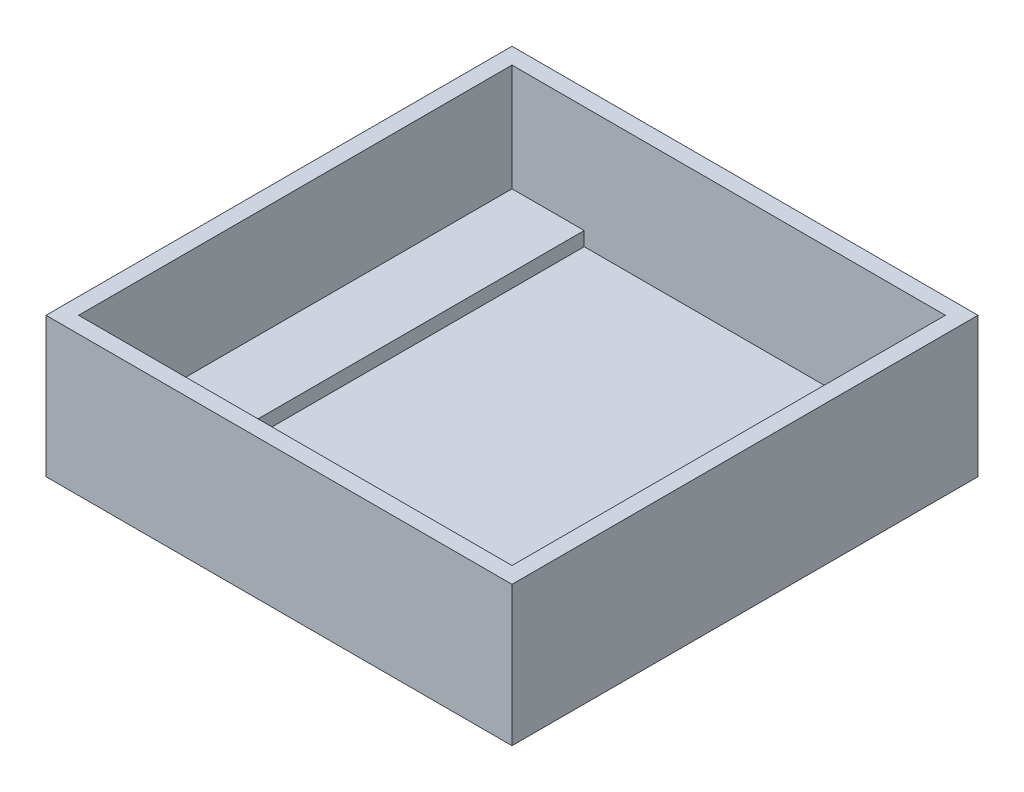
SolidWorks part; units mm, degrees
ref_plane "Front Plane" through (0, 0, 0) normal (0, 0, 1) x (1, 0, 0)
ref_plane "Top Plane" through (0, 0, 0) normal (0, 1, 0) x (1, 0, 0)
ref_plane "Right Plane" through (0, 0, 0) normal (1, 0, 0) x (0, 0, -1)
sketch "Sketch1" plane through (0, 0, 0) normal (0, 1, 0) x (1, 0, 0)
  line L0 (-310, 465) -> (-465, 465)
  line L1 (-500, -500) -> (500, -500)
  line L2 (-500, -500) -> (-500, 500)
  line L3 (-500, 500) -> (500, 500)
  line L4 (500, -500) -> (500, 500)
  line L5 (-500, -500) -> (500, 500) construction
  line L6 (-500, 500) -> (500, -500) construction
  line L7 (-310, -465) -> (310, -465)
  line L8 (-310, -465) -> (-310, 465)
  line L9 (-310, 465) -> (310, 465)
  line L10 (310, -465) -> (310, 465)
  line L11 (-310, -465) -> (310, 465) construction
  line L12 (-310, 465) -> (310, -465) construction
  line L13 (-465, 465) -> (-465, -465)
  line L14 (-465, -465) -> (-310, -465)
  line L15 (310, -465) -> (465, -465)
  line L16 (465, -465) -> (465, 465)
  line L17 (465, 465) -> (310, 465)
  point P0 (0, 0)
  point P6 (0, 0)
  dimension "D1" = 1000
  dimension "D2" = 930
  dimension "D3" = 620
extrude "Boss-Extrude2" add sketch "Sketch1" along normal blind 300 contours L1 L4 L3 L2 L17 L16 L15 L7 L14 L13 L0 L9 region at (-485.8579, 0, 0)
extrude "Boss-Extrude3" add sketch "Sketch1<4>" along normal blind 70 contours L13 L14 L8 L0 | L16 L17 L10 L15 region at (-387.5, 0, 0) region at (387.5, 0, 0)
sketch "Sketch1<4>" plane through (0, 0, 0) normal (0, 1, 0) x (1, 0, 0) same geometry as "Sketch1"
extrude "Boss-Extrude4" add sketch "Sketch1<5>" along normal blind 40 contours L7 L10 L9 L8 region at (0, 0, 0)
sketch "Sketch1<5>" plane through (0, 0, 0) normal (0, 1, 0) x (1, 0, 0) same geometry as "Sketch1"
